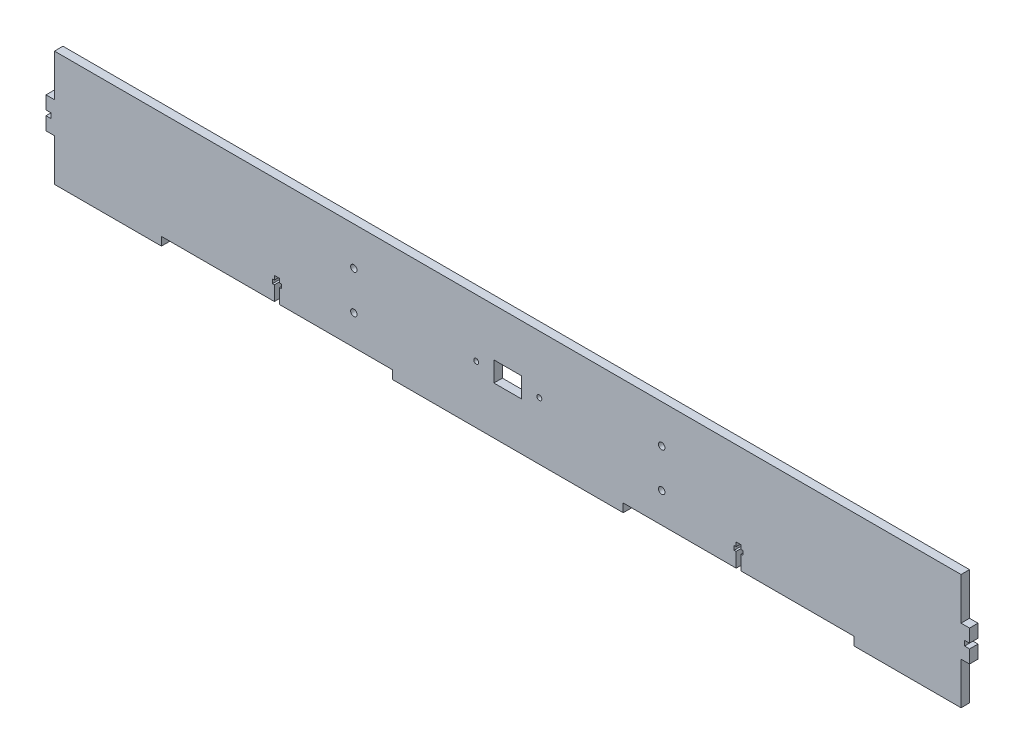
SolidWorks part; units mm, degrees
ref_plane "Front Plane" through (0, 0, 0) normal (0, 0, 1) x (1, 0, 0)
ref_plane "Top Plane" through (0, 0, 0) normal (0, 1, 0) x (1, 0, 0)
ref_plane "Right Plane" through (0, 0, 0) normal (1, 0, 0) x (0, 0, -1)
sketch "Sketch1" plane through (0, 0, 0) normal (0, 0, 1) x (1, 0, 0)
  line L0 (308.5, 78) -> (308.5, 50.625)
  line L1 (308.5, 50.625) -> (303, 50.625)
  line L2 (303, 50.625) -> (303, 42.125)
  line L3 (303, 42.125) -> (306.25, 42.125)
  line L4 (306.25, 42.125) -> (306.25, 40.5)
  line L5 (306.25, 40.5) -> (306.25, 38.875)
  line L6 (306.25, 38.875) -> (303, 38.875)
  line L7 (303, 38.875) -> (303, 30.375)
  line L8 (303, 30.375) -> (308.5, 30.375)
  line L9 (308.5, 30.375) -> (308.5, 3)
  line L10 (308.5, 3) -> (378, 3)
  line L11 (378, 3) -> (378, 8.5)
  line L12 (378, 8.5) -> (451.375, 8.5)
  line L13 (451.375, 8.5) -> (451.375, 17.95)
  line L14 (451.375, 17.95) -> (450.125, 17.95)
  line L15 (450.125, 17.95) -> (450.125, 20.6)
  line L16 (450.125, 20.6) -> (451.375, 20.6)
  line L17 (451.375, 20.6) -> (451.375, 23.25)
  line L18 (451.375, 23.25) -> (454.625, 23.25)
  line L19 (454.625, 23.25) -> (454.625, 20.6)
  line L20 (454.625, 20.6) -> (455.875, 20.6)
  line L21 (455.875, 20.6) -> (455.875, 17.95)
  line L22 (455.875, 17.95) -> (454.625, 17.95)
  line L23 (454.625, 17.95) -> (454.625, 8.5)
  line L24 (454.625, 8.5) -> (528, 8.5)
  line L25 (528, 8.5) -> (528, 3)
  line L26 (528, 3) -> (678, 3)
  line L27 (678, 3) -> (678, 8.5)
  line L28 (678, 8.5) -> (751.375, 8.5)
  line L29 (751.375, 8.5) -> (751.375, 17.95)
  line L30 (751.375, 17.95) -> (750.125, 17.95)
  line L31 (750.125, 17.95) -> (750.125, 20.6)
  line L32 (750.125, 20.6) -> (751.375, 20.6)
  line L33 (751.375, 20.6) -> (751.375, 23.25)
  line L34 (751.375, 23.25) -> (754.625, 23.25)
  line L35 (754.625, 23.25) -> (754.625, 20.6)
  line L36 (754.625, 20.6) -> (755.875, 20.6)
  line L37 (755.875, 20.6) -> (755.875, 17.95)
  line L38 (755.875, 17.95) -> (754.625, 17.95)
  line L39 (754.625, 17.95) -> (754.625, 8.5)
  line L40 (754.625, 8.5) -> (828, 8.5)
  line L41 (828, 8.5) -> (828, 3)
  line L42 (828, 3) -> (897.5, 3)
  line L43 (897.5, 3) -> (897.5, 30.375)
  line L44 (897.5, 30.375) -> (903, 30.375)
  line L45 (903, 30.375) -> (903, 38.875)
  line L46 (903, 38.875) -> (899.75, 38.875)
  line L47 (899.75, 38.875) -> (899.75, 40.5)
  line L48 (899.75, 40.5) -> (899.75, 42.125)
  line L49 (899.75, 42.125) -> (903, 42.125)
  line L50 (903, 42.125) -> (903, 50.625)
  line L51 (903, 50.625) -> (897.5, 50.625)
  line L52 (897.5, 50.625) -> (897.5, 78)
  line L53 (897.5, 78) -> (308.5, 78)
extrude "Boss-Extrude1" add sketch "Sketch1" along normal blind 5.5
sketch "Sketch2" plane through (0, 0, 5.5) normal (0, 0, 1) x (1, 0, 0)
  line L0 (582.5, 40.5) -> (623.5, 40.5)
  line L1 (897.5, 78) -> (308.5, 78) construction
  line L2 (306.25, 42.125) -> (306.25, 38.875) construction
  line L4 (594, 47) -> (612, 47)
  line L5 (594, 47) -> (594, 34)
  line L6 (594, 34) -> (612, 34)
  line L7 (612, 47) -> (612, 34)
  circle A0 centre (582.5, 40.5) radius 1.6
  circle A1 centre (623.5, 40.5) radius 1.6
  point P4 (603, 40.5)
  point P7 (603, 78)
  point P8 (612, 40.5)
  point P11 (306.25, 40.5)
  point P16 (603, 47)
  dimension "D1" = 3.2
  dimension "D2" = 41
  dimension "D3" = 13
  dimension "D4" = 18
extrude "Cut-Extrude1" cut sketch "Sketch2" against normal through all both and the other way through all contours A1 | A0 | L7 L0 L5 L6 | L7 L4 L5 L0 region at (623.5, 42.0547, 5.5) region at (603, 43.75, 5.5) region at (603, 37.25, 5.5) region at (580.9453, 40.5, 5.5)
sketch "Sketch3" plane through (0, 0, 5.5) normal (0, 0, 1) x (1, 0, 0)
  line L1 (503, 53) -> (703, 53)
  line L2 (503, 53) -> (503, 28)
  line L3 (503, 28) -> (703, 28)
  line L4 (703, 53) -> (703, 28)
  line L5 (897.5, 78) -> (308.5, 78) construction
  circle A0 centre (503, 53) radius 2.1
  circle A1 centre (503, 28) radius 2.1
  circle A2 centre (703, 28) radius 2.1
  circle A3 centre (703, 53) radius 2.1
  point P4 (603, 53)
  point P7 (603, 78)
  dimension "D4" = 4.2
  dimension "D1" = 25
  dimension "D2" = 200
  dimension "D3" = 25
extrude "Cut-Extrude2" cut sketch "Sketch3" against normal through all contours A0 | A1 | A2 | A3
